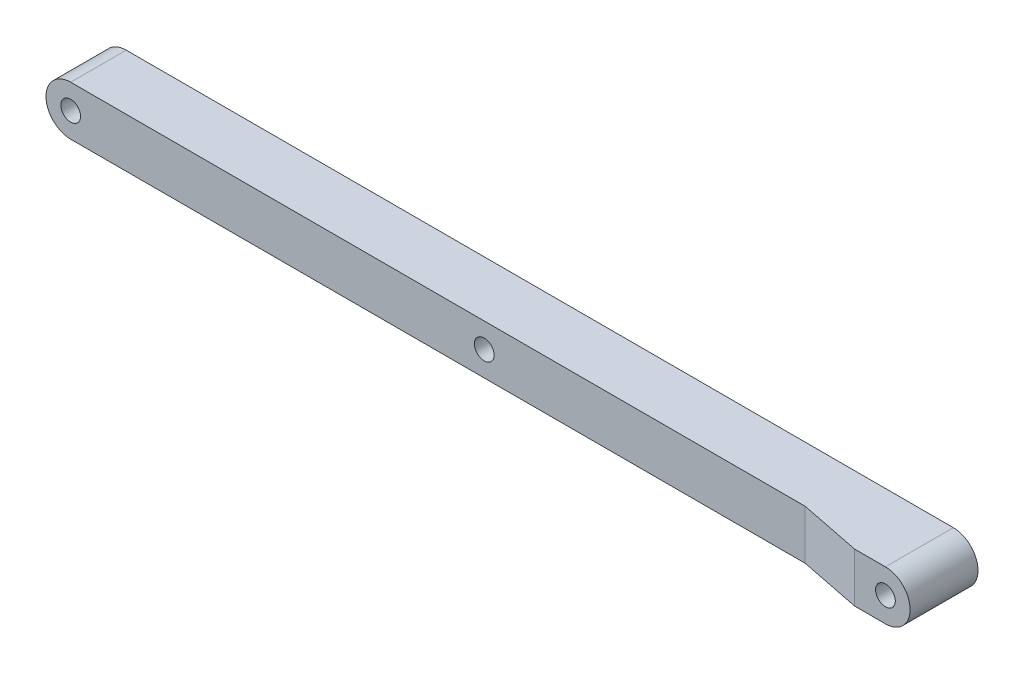
SolidWorks part; units mm, degrees
ref_plane "前基準面" through (0, 0, 0) normal (0, 0, 1) x (1, 0, 0)
ref_plane "上基準面" through (0, 0, 0) normal (0, 1, 0) x (1, 0, 0)
ref_plane "右基準面" through (0, 0, 0) normal (1, 0, 0) x (0, 0, -1)
sketch "草圖1" plane through (0, 0, 0) normal (0, 0, 1) x (1, 0, 0)
  line L0 (-53.1113, 0) -> (80.8887, 0) construction
  line L1 (-53.1113, 4) -> (80.8887, 4)
  line L2 (-53.1113, -4) -> (80.8887, -4)
  arc A0 (-53.1113, 4) -> (-53.1113, -4) centre (-53.1113, 0) ccw
  arc A1 (80.8887, -4) -> (80.8887, 4) centre (80.8887, 0) ccw
  circle A2 centre (80.8887, 0) radius 2.75
  circle A3 centre (-53.1113, 0) radius 1.6
  circle A4 centre (13.8887, 0) radius 1.6
  point P3 (13.8887, 0)
  dimension "D2" = 4
  dimension "D3" = 3.2
  dimension "D4" = 5.5
  dimension "D5" = 3.2
  dimension "D1" = 134
extrude "填料-伸長1" add sketch "草圖1" along normal blind 11
sketch "草圖2" plane through (0, 0, 11) normal (0, 0, 1) x (1, 0, 0)
  circle A0 centre (80.8887, 0) radius 2.75
  circle A1 centre (80.8887, 0) radius 1.6
  dimension "D1" = 3.2
extrude "填料-伸長2" add sketch "草圖2" against normal blind 7
sketch "草圖3" plane through (0, 0, 11) normal (0, 0, 1) x (1, 0, 0)
  line L0 (65.8887, 4) -> (65.8887, -4)
  line L1 (65.8887, 4) -> (-61.1113, 4)
  line L2 (65.8887, -4) -> (-61.1113, -4)
  line L3 (-61.1113, 4) -> (-61.1113, -4)
  line L4 (80.8887, 4) -> (-53.1113, 4) construction
  line L5 (-53.1113, -4) -> (80.8887, -4) construction
  circle A0 centre (-53.1113, 0) radius 1.6 construction
  circle A1 centre (80.8887, 0) radius 1.6 construction
  dimension "D1" = 8
  dimension "D2" = 15
extrude "除料-伸長1" cut sketch "草圖3" against normal blind 2
chamfer "導角1" distance 10 distance2 2 1 edges at (65.8887, 0, 11) first distance on face at (74.3887, 0, 11)
